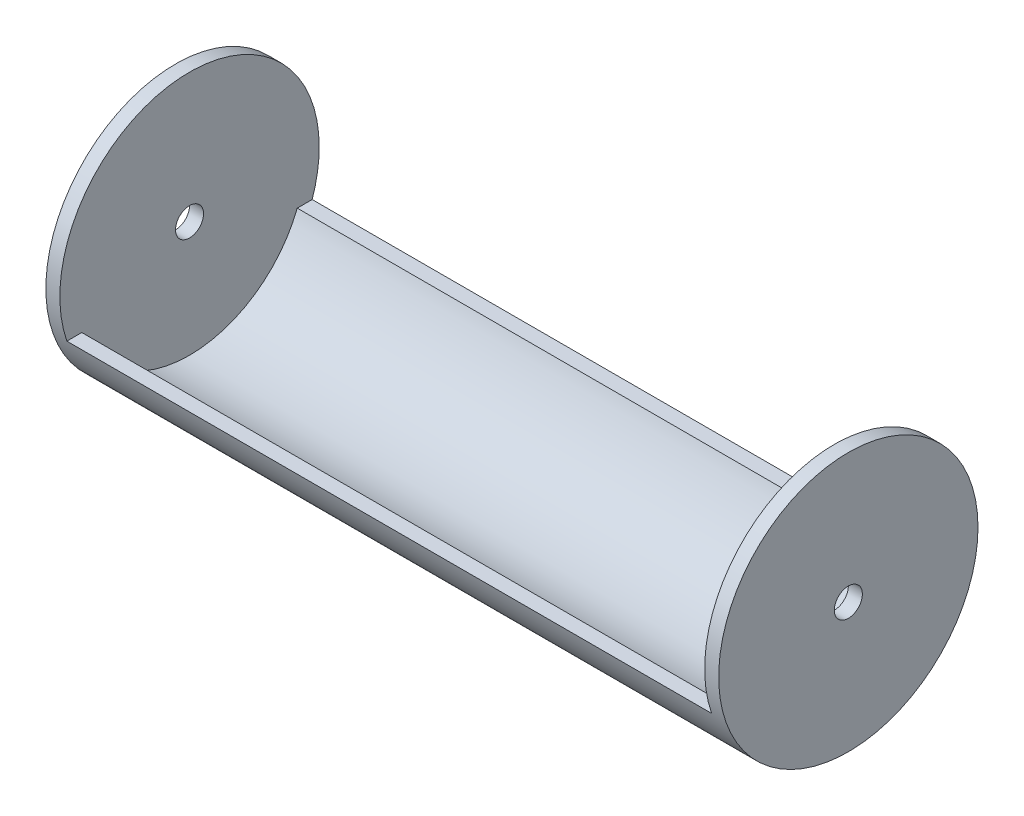
SolidWorks part; units mm, degrees
material "CMR DEFAULT - CHANGE MATERIAL"
ref_plane "XY PLANE - TOP" through (0, 0, 0) normal (0, 0, 1) x (1, 0, 0)
ref_plane "XZ PLANE - SIDE" through (0, 0, 0) normal (0, 1, 0) x (1, 0, 0)
ref_plane "YZ PLANE - FRONT" through (0, 0, 0) normal (1, 0, 0) x (0, 0, -1)
sketch "Sketch1" plane through (0, 0, 0) normal (1, 0, 0) x (0, 0, -1)
  circle A0 centre (0, 0) radius 58.7375
  circle A1 centre (0, 0) radius 6.35
  dimension "D1" = 117.475
  dimension "D2" = 12.7
extrude "Boss-Extrude1" add sketch "Sketch1" along normal mid plane 304.8
sketch "Sketch2" plane through (0, 0, 0) normal (0, 0, 1) x (1, 0, 0)
  line L0 (152.4, 58.7375) -> (-152.4, 58.7375) construction
  line L1 (-146.05, 58.7375) -> (146.05, 58.7375)
  line L2 (-146.05, 58.7375) -> (-146.05, -19.05)
  line L3 (-146.05, -19.05) -> (146.05, -19.05)
  line L4 (146.05, 58.7375) -> (146.05, -19.05)
  line L5 (0, -19.05) -> (0, 58.7375) construction
  line L6 (-146.05, 19.8438) -> (146.05, 19.8438) construction
  line L7 (0, -55) -> (0, 55) construction
  line L8 (-152.4, 58.7375) -> (-152.4, -58.7375) construction
  line L10 (88.5065, 0) -> (-88.5065, 0) construction
  point P284 (0, 19.8438)
  dimension "D1" = 6.35
  dimension "D2" = 19.05
extrude "Cut-Extrude1" cut sketch "Sketch2" against normal through all both and the other way through all
shell "Shell1" thickness 6.35 removed face at (0, -19.05, 0)
